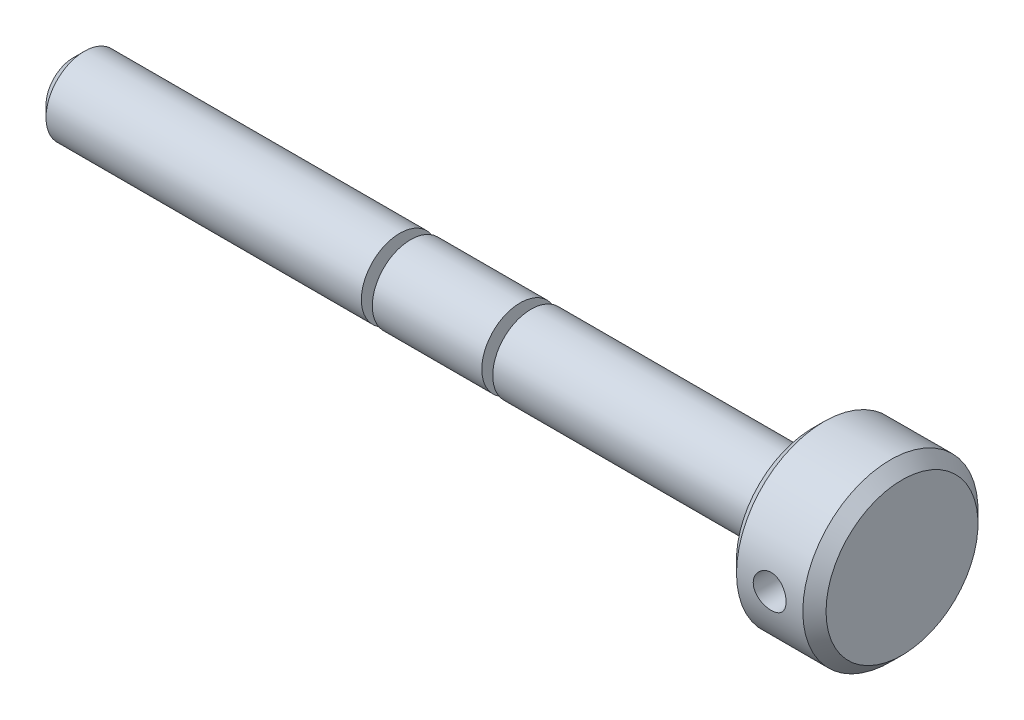
SolidWorks part; units mm, degrees
ref_plane "Front Plane" through (0, 0, 0) normal (0, 0, 1) x (1, 0, 0)
ref_plane "Top Plane" through (0, 0, 0) normal (0, 1, 0) x (1, 0, 0)
ref_plane "Right Plane" through (0, 0, 0) normal (1, 0, 0) x (0, 0, -1)
sketch "Sketch2" plane through (0, 0, 0) normal (0, 0, 1) x (1, 0, 0)
  line L0 (-76.639, 0) -> (74.715, 0)
  line L1 (74.715, 0) -> (74.715, 16)
  line L2 (74.715, 16) -> (58.361, 16)
  line L3 (58.361, 16) -> (58.361, 7)
  line L4 (58.361, 7) -> (6.961, 7)
  line L5 (6.961, 7) -> (6.961, 2.9917)
  line L6 (6.961, 2.9917) -> (4.961, 2.9917)
  line L7 (4.961, 2.9917) -> (4.961, 7)
  line L8 (4.961, 7) -> (-15.039, 7)
  line L9 (-15.039, 7) -> (-15.039, 2.9917)
  line L10 (-15.039, 2.9917) -> (-17.039, 2.9917)
  line L11 (-17.039, 2.9917) -> (-17.039, 7)
  line L12 (-17.039, 7) -> (-76.639, 7)
  line L13 (-76.639, 7) -> (-76.639, 0)
  dimension "D1" = 135
  dimension "D2" = 16
  dimension "D3" = 7
  dimension "D4" = 20
  dimension "D5" = 51.4
  dimension "D6" = 2
  dimension "D7" = 2
revolve "Revolve1" add sketch "Sketch2" angle 360 about L0
cosmetic thread "Cosmetic Thread1" parameters "D1"=5, "D2"=11.797
chamfer "Chamfer1" distance 2 angle 45 1 edges at (-76.639, 0, 7)
chamfer "Chamfer2" distance 2.1213 angle 45 2 edges at (58.361, 0, 16) (74.715, 0, 16)
sketch "Sketch3" plane through (0, 0, 0) normal (0, 0, 1) x (1, 0, 0)
  circle A0 centre (66.538, 0) radius 3
  dimension "D1" = 6
extrude "Cut-Extrude1" cut sketch "Sketch3" against normal blind 135 and the other way blind 135
